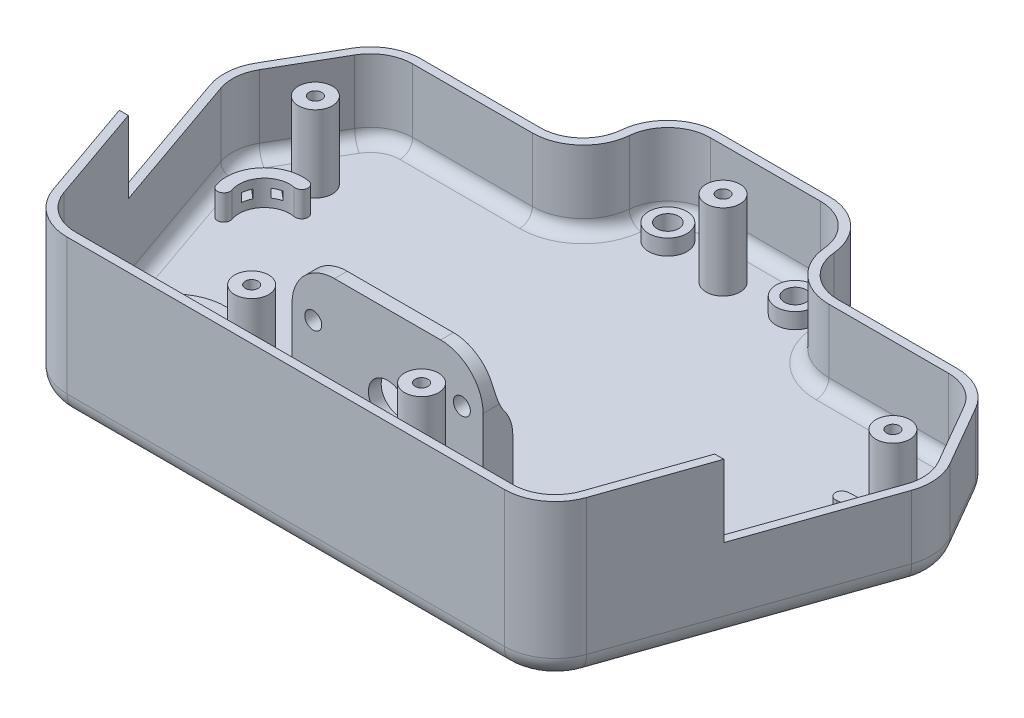
SolidWorks part; units mm, degrees
ref_plane "Front Plane" through (0, 0, 0) normal (0, 0, 1) x (1, 0, 0)
ref_plane "Top Plane" through (0, 0, 0) normal (0, 1, 0) x (1, 0, 0)
ref_plane "Right Plane" through (0, 0, 0) normal (1, 0, 0) x (0, 0, -1)
sketch "Sketch1" plane through (0, 0, 0) normal (0, 1, 0) x (1, 0, 0)
  line L0 (-70, -55) -> (-25, -55)
  line L1 (70, -55) -> (84.4338, -80)
  line L2 (84.4338, -80) -> (60, -150)
  line L3 (60, -150) -> (-60, -150)
  line L4 (-60, -150) -> (-84.4338, -80)
  line L5 (-84.4338, -80) -> (-70, -55)
  line L6 (-25, -55) -> (-25, -35)
  line L7 (-25, -35) -> (25, -35)
  line L8 (25, -35) -> (25, -55)
  line L9 (0, -55) -> (0, -122.8119) construction
  line L10 (25, -55) -> (70, -55)
  point P15 (0, -150)
  dimension "D1" = 25
  dimension "D2" = 140
  dimension "D3" = 70
  dimension "D4" = 120
  dimension "D5" = 70
  dimension "D6" = 55
  dimension "D7" = 120
  dimension "D8" = 20
  dimension "D9" = 50
  dimension "D10" = 25
extrude "Boss-Extrude1" add sketch "Sketch1" along normal blind 2
sketch "Sketch2" plane through (0, 2, 0) normal (0, 1, 0) x (1, 0, 0)
  line L0 (84.4338, -80) -> (70, -55) construction
  line L1 (60, -150) -> (84.4338, -80) construction
  line L2 (-60, -150) -> (60, -150) construction
  line L3 (-84.4338, -80) -> (-60, -150) construction
  line L4 (-70, -55) -> (-84.4338, -80) construction
  line L6 (84.4338, -80) -> (70, -55)
  line L7 (60, -150) -> (84.4338, -80)
  line L8 (-60, -150) -> (60, -150)
  line L9 (-84.4338, -80) -> (-60, -150)
  line L10 (-70, -55) -> (-84.4338, -80)
  line L11 (70, -55) -> (25, -55)
  line L12 (68.8453, -57) -> (23, -57)
  line L13 (-68.8453, -57) -> (-82.2434, -80.2062)
  line L14 (-82.2434, -80.2062) -> (-58.5798, -148)
  line L15 (-58.5798, -148) -> (58.5798, -148)
  line L16 (58.5798, -148) -> (82.2434, -80.2062)
  line L17 (82.2434, -80.2062) -> (68.8453, -57)
  line L18 (-25, -55) -> (-25, -35)
  line L19 (-25, -35) -> (25, -35)
  line L20 (25, -35) -> (25, -55)
  line L21 (-25, -55) -> (-70, -55)
  line L22 (-23, -57) -> (-23, -37)
  line L23 (70, -55) -> (-70, -55) construction
  line L24 (-23, -37) -> (23, -37)
  line L25 (23, -37) -> (23, -57)
  line L26 (-23, -57) -> (-68.8453, -57)
  line L28 (68.8453, -57) -> (-68.8453, -57) construction
  dimension "D1" = 2
  dimension "D2" = 2
  dimension "D3" = 2
  dimension "D4" = 2
extrude "Boss-Extrude2" add sketch "Sketch2" along normal blind 35
sketch "Sketch3" plane through (0, 2, 0) normal (0, 1, 0) x (1, 0, 0)
  line L0 (-70, -90.472) -> (70, -90.472) construction
  line L1 (-70, -55) -> (-70, -122.5477) construction
  line L2 (70, -55) -> (70, -124.9619) construction
  line L4 (0, -90.472) -> (0, -37.8941) construction
  line L5 (25, -35) -> (-25, -35) construction
  circle A0 centre (-15, -45) radius 4.5
  circle A1 centre (15, -45) radius 4.5
  dimension "D1" = 9
  dimension "D2" = 30
  dimension "D3" = 15
  dimension "D4" = 10
extrude "Boss-Extrude3" add sketch "Sketch3" along normal blind 5.7 from surface starting at face at (0, 0, 75)
sketch "Sketch5" plane through (0, 5.7, 0) normal (0, 1, 0) x (1, 0, 0)
  circle A0 centre (-15, -45) radius 2.55
  circle A1 centre (15, -45) radius 2.55
  circle A2 centre (-15, -45) radius 4.5 construction
  circle A3 centre (15, -45) radius 4.5 construction
  dimension "D1" = 5.1
extrude "Cut-Extrude1" cut sketch "Sketch5" against normal through all
sketch "Sketch6" plane through (0, 2, 0) normal (0, 1, 0) x (1, 0, 0)
  line L0 (-84.4338, -80) -> (-84.4338, -51.4786) construction
  line L1 (84.4338, -80) -> (84.4338, -51.4786) construction
  line L18 (-65, -90) -> (-63.88, -84.1055) construction
  line L19 (-65, -90) -> (-70.6648, -91.9773) construction
  line L20 (-82.2434, -80.2062) -> (-58.5798, -148) construction
  line L21 (0, -59.2619) -> (0, -121.1294) construction
  arc A2 (-63.88, -84.1055) -> (-70.6648, -91.9773) centre (-65, -90) ccw
  arc A3 (-63.32, -81.1582) -> (-73.4972, -92.966) centre (-65, -90) ccw
  arc A4 (-73.4972, -92.966) -> (-70.6648, -91.9773) centre (-72.081, -92.4717) ccw
  arc A5 (-63.88, -84.1055) -> (-63.32, -81.1582) centre (-63.6, -82.6318) ccw
  circle A6 centre (15, -45) radius 2.55 construction
  circle A7 centre (-15, -45) radius 2.55 construction
  circle A8 centre (15, -45) radius 2.55 construction
  circle A9 centre (-15, -45) radius 2.55 construction
  dimension "D1" = 3
  dimension "D3" = 6
  dimension "D4" = 80
  dimension "D2" = 120
  dimension "D5" = 45
extrude "Boss-Extrude4" add sketch "Sketch6" along normal blind 6
ref_plane "Plane1" through (5.5088, 0, 4.7481) normal (0.7575, 0, 0.6529) x (0.6529, 0, -0.7575)
sketch "Sketch7" plane through (5.5088, 0, 4.7481) normal (0.7575, 0, 0.6529) x (0.6529, 0, -0.7575)
  line L1 (-88.1228, 2) -> (-114.4481, 2) construction
  line L2 (-88.1228, 2) -> (-159.2312, 2) construction
  line L3 (-115.805, 8) -> (-115.805, 2) construction
  line L4 (-105.4127, 8) -> (-105.4127, 2) construction
  line L5 (-115.805, 8) -> (-115.805, 2) construction
  line L6 (-105.4127, 8) -> (-105.4127, 2) construction
  line L7 (-114.1089, 6) -> (-115.805, 6) construction
  line L8 (-114.1089, 6) -> (-112.1089, 6)
  line L9 (-114.1089, 6) -> (-114.1089, 4)
  line L10 (-114.1089, 4) -> (-112.1089, 4)
  line L11 (-112.1089, 6) -> (-112.1089, 4)
  line L12 (-109.1089, 6) -> (-107.1089, 6)
  line L13 (-109.1089, 6) -> (-109.1089, 4)
  line L14 (-109.1089, 4) -> (-107.1089, 4)
  line L15 (-107.1089, 6) -> (-107.1089, 4)
  line L16 (-107.1089, 6) -> (-105.4127, 6) construction
  dimension "D1" = 3
  dimension "D2" = 2
  dimension "D3" = 2
  dimension "D4" = 2
  dimension "D5" = 2
extrude "Cut-Extrude2" cut sketch "Sketch7" against normal up to surface (6.6241 mm away) up to face at (-70.1129, 5, 85.5931)
ref_plane "Plane2" through (0, 0, 0) normal (1, 0, 0) x (0, 0, -1)
ref_plane "Plane3" through (0, 0, 126) normal (0, 0, -1) x (-1, 0, 0)
sketch "Sketch8" plane through (0, 0, 126) normal (0, 0, -1) x (-1, 0, 0)
  line L0 (-68.8453, 2) -> (-23, 2) construction
  line L1 (-68.8453, 2) -> (-23, 2) construction
  line L2 (60, 0) -> (-60, 0) construction
  line L3 (22.5, 2) -> (-22.5, 2)
  line L4 (22.5, 2) -> (22.5, 36)
  line L5 (22.5, 36) -> (-22.5, 36)
  line L6 (-22.5, 2) -> (-22.5, 36)
  line L7 (60, 0) -> (-60, 0) construction
  line L8 (0, 14.8493) -> (0, -14.8493) construction
  dimension "D1" = 34
  dimension "D2" = 45
  dimension "D3" = 22.5
extrude "Boss-Extrude5" add sketch "Sketch8" along normal blind 3
sketch "Sketch9" plane through (0, 2, 0) normal (0, 1, 0) x (1, 0, 0)
  line L1 (-22.5, -123) -> (-19.5, -123)
  line L2 (-22.5, -123) -> (-22.5, -119)
  line L3 (-22.5, -119) -> (-19.5, -119)
  line L4 (-19.5, -123) -> (-19.5, -119)
  line L5 (22.5, -123) -> (19.5, -123)
  line L6 (22.5, -123) -> (22.5, -119)
  line L7 (22.5, -119) -> (19.5, -119)
  line L8 (19.5, -123) -> (19.5, -119)
  dimension "D1" = 3
  dimension "D2" = 4
extrude "Boss-Extrude6" add sketch "Sketch9" along normal blind 20
fillet "Fillet1" radius 10 2 edges at (-21, 22, 123) (21, 22, 123)
fillet "Fillet2" radius 10 2 edges at (-21, 22, 119) (21, 22, 119)
sketch "Sketch11" plane through (0, 2, 0) normal (0, 1, 0) x (1, 0, 0)
  line L0 (-58.5798, -148) -> (58.5798, -148) construction
  circle A0 centre (-43.5798, -133) radius 12.5
  dimension "D1" = 25
  dimension "D2" = 15
  dimension "D3" = 15
extrude "Boss-Extrude9" add sketch "Sketch11" along normal blind 10
ref_plane "Plane4" through (0, 7, 0) normal (0, 1, 0) x (1, 0, 0)
sketch "Sketch13" plane through (0, 7, 0) normal (0, 1, 0) x (1, 0, 0)
  line L0 (-53.0211, -136.2955) -> (-58.294, -121.1894)
  line L1 (-82.2434, -80.2062) -> (-58.5798, -148) construction
  line L2 (-34.1384, -129.7045) -> (-39.4113, -114.5983)
  line L3 (-58.294, -121.1894) -> (-39.4113, -114.5983)
  arc A0 (-53.0211, -136.2955) -> (-34.1384, -129.7045) centre (-43.5798, -133) ccw
  dimension "D1" = 20
  dimension "D2" = 16
extrude "Cut-Extrude3" cut sketch "Sketch13" along normal blind 5 from offset 3 offset against normal yes
sketch "Sketch14" plane through (0, 12, 0) normal (0, 1, 0) x (1, 0, 0)
  circle A0 centre (-43.5798, -133) radius 2.5
  circle A1 centre (-43.5798, -133) radius 12.5 construction
  dimension "D1" = 5
extrude "Cut-Extrude4" cut sketch "Sketch14" against normal up to surface (8 mm away) up to face at (-44.4037, 4, 130.6397)
sketch "Sketch15" plane through (0, 0, 126) normal (0, 0, 1) x (1, 0, 0)
  line L1 (22.5, 2) -> (-22.5, 2) construction
  line L2 (22.5, 2) -> (-22.5, 2) construction
  line L3 (0, -14.8493) -> (0, 14.8493) construction
  circle A0 centre (17.5, 25) radius 2
  circle A1 centre (-17.5, 25) radius 2
  circle A3 centre (0, 17) radius 4.5
  dimension "D1" = 8
  dimension "D2" = 4
  dimension "D3" = 4
  dimension "D6" = 9
  dimension "D4" = 35
  dimension "D5" = 17.5
  dimension "D7" = 15
extrude "Cut-Extrude5" cut sketch "Sketch15" against normal up to surface (3 mm away) up to face at (0, 24.5, 123)
mirror "Mirror1" about plane through (0, 0, 0) normal (1, 0, 0) of "Cut-Extrude4", "Cut-Extrude3", "Boss-Extrude9", "Cut-Extrude2", "Boss-Extrude4"
fillet "Fillet3" radius 10 10 edges at (-23, 19.5, 37) (23, 19.5, 37) (-25, 18.5, 55) (25, 18.5, 55) (58.5798, 19.5, 148) (-58.5798, 19.5, 148) (82.2434, 19.5, 80.2062) (68.8453, 19.5, 57) (-82.2434, 19.5, 80.2062) (-68.8453, 19.5, 57)
fillet "Fillet4" radius 12 10 edges at (-60, 18.5, 150) (-84.4338, 18.5, 80) (-70, 18.5, 55) (-23, 19.5, 57) (-25, 18.5, 35) (25, 18.5, 35) (23, 19.5, 57) (70, 18.5, 55) (60, 18.5, 150) (84.4338, 18.5, 80)
fillet "Fillet5" radius 10 2 edges at (22.5, 36, 124.5) (-22.5, 36, 124.5)
fillet "Fillet6" radius 3 18 edges at (-70.8266, 2, 112.9143) (-81.2478, 2, 80.3) (-75.842, 2, 69.1187) (-68.0718, 2, 58.3397) (-48.9903, 2, 57) (-26.8185, 2, 53.8626) (0, 2, 37) (26.8185, 2, 53.8626) (48.9903, 2, 57) (68.0718, 2, 58.3397) (75.842, 2, 69.1187) (81.2478, 2, 80.3) (70.8266, 2, 112.9143) (0, 2, 148) (-57.2685, 2, 146.1534) (57.2685, 2, 146.1534) (-19.742, 2, 39.6145) (19.742, 2, 39.6145)
fillet "Fillet7" radius 5 18 edges at (69.0718, 0, 56.6077) (77.5741, 0, 68.1187) (83.2389, 0, 80.1125) (72.7148, 0, 113.5734) (58.4264, 0, 147.7841) (0, 0, 150) (-58.4264, 0, 147.7841) (-72.7148, 0, 113.5734) (-83.2389, 0, 80.1125) (-77.5741, 0, 68.1187) (-69.0718, 0, 56.6077) (-49.0359, 0, 55) (-28.258, 0, 52.3855) (-21.1815, 0, 38.1374) (0, 0, 35) (21.1815, 0, 38.1374) (28.258, 0, 52.3855) (49.0359, 0, 55)
sketch "Sketch16" plane through (0, 0, 0) normal (1, 0, 0) x (0, 0, -1)
  line L0 (-83.5443, 0) -> (-140.3069, 0) construction
  line L1 (-118, 40) -> (-28, 40)
  line L2 (-118, 40) -> (-118, 20)
  line L3 (-118, 20) -> (-28, 20)
  line L4 (-28, 40) -> (-28, 20)
  line L5 (-150, 5) -> (-150, 37) construction
  dimension "D1" = 20
  dimension "D2" = 32
  dimension "D3" = 20
  dimension "D4" = 90
extrude "Cut-Extrude6" cut sketch "Sketch16" against normal through all both and the other way through all
sketch "Sketch17" plane through (0, 2, 0) normal (0, 1, 0) x (1, 0, 0)
  line L0 (0, -14.8493) -> (0, 14.8493) construction
  line L3 (-13.0911, -35) -> (13.0911, -35) construction
  line L4 (-63.0718, -55) -> (-35, -55) construction
  circle A0 centre (0, -47) radius 4
  circle A1 centre (0, -47) radius 1.5
  circle A2 centre (-68, -75) radius 4
  circle A4 centre (-68, -75) radius 1.5
  circle A10 centre (68, -75) radius 1.5
  circle A11 centre (68, -75) radius 4
  dimension "D1" = 8
  dimension "D3" = 3
  dimension "D7" = 8
  dimension "D9" = 3
  dimension "D2" = 12
  dimension "D4" = 20
  dimension "D5" = 68
extrude "Boss-Extrude10" add sketch "Sketch17" along normal up to surface (18 mm away) up to face at (0, 20, 66.5912)
sketch "Sketch19" plane through (0, 2, 0) normal (0, 1, 0) x (1, 0, 0)
  line L0 (0, -14.8493) -> (0, 14.8493) construction
  line L1 (-51.4786, -150) -> (51.4786, -150) construction
  circle A0 centre (-20, -138) radius 4
  circle A1 centre (-20, -138) radius 1.5
  circle A2 centre (20, -138) radius 1.5
  circle A3 centre (20, -138) radius 4
  dimension "D1" = 3
  dimension "D2" = 8
  dimension "D3" = 20
  dimension "D4" = 12
extrude "Boss-Extrude11" add sketch "Sketch19" along normal up to surface (35 mm away) up to face at (0, 37, 136.7604)
